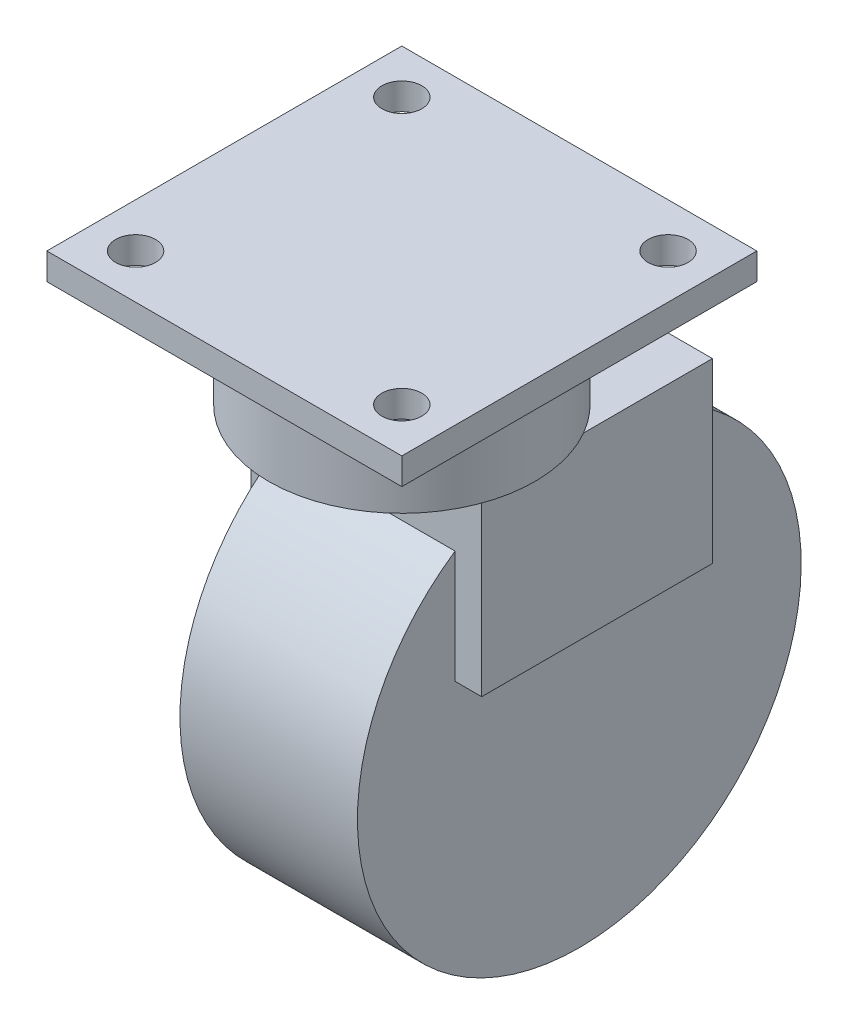
SolidWorks part; units mm, degrees
ref_plane "Front Plane" through (0, 0, 0) normal (0, 0, 1) x (1, 0, 0)
ref_plane "Top Plane" through (0, 0, 0) normal (0, 1, 0) x (1, 0, 0)
ref_plane "Right Plane" through (0, 0, 0) normal (1, 0, 0) x (0, 0, -1)
sketch "SK_Plate" plane through (0, 0, 0) normal (0, 1, 0) x (1, 0, 0)
  line L1 (-20, 20) -> (20, 20)
  line L2 (-20, 20) -> (-20, -20)
  line L3 (-20, -20) -> (20, -20)
  line L4 (20, 20) -> (20, -20)
  dimension "D1" = 40
  dimension "D2" = 40
  dimension "D3" = 20
  dimension "D4" = 20
extrude "EX_Plate" add sketch "SK_Plate" against normal blind 3
sketch "SK_PlateHoles_4x" plane through (0, 0, 0) normal (0, 1, 0) x (1, 0, 0)
  circle A0 centre (15, -15) radius 2.25
  circle A1 centre (-15, -15) radius 2.25
  circle A2 centre (15, 15) radius 2.25
  circle A3 centre (-15, 15) radius 2.25
  dimension "D3" = 4.5
  dimension "D6" = 4.5
  dimension "D9" = 4.5
  dimension "D12" = 4.5
  dimension "D1" = 15
  dimension "D2" = 15
  dimension "D4" = 15
  dimension "D5" = 15
  dimension "D7" = 15
  dimension "D8" = 15
  dimension "D10" = 15
  dimension "D11" = 15
extrude "CUT_PlateHoles_4x" cut sketch "SK_PlateHoles_4x" against normal blind 3
ref_plane "PL_Zm3" through (0, -3, 0) normal (0, 1, 0) x (1, 0, 0)
sketch "SK_Swivel" plane through (0, -3, 0) normal (0, 1, 0) x (1, 0, 0)
  circle A0 centre (0, 0) radius 15
  dimension "D1" = 30
extrude "EX_Swivel" add sketch "SK_Swivel" against normal blind 12
ref_plane "PL_Zm15" through (0, -15, 0) normal (0, 1, 0) x (1, 0, 0)
sketch "SK_Fork" plane through (0, -15, 0) normal (0, 1, 0) x (1, 0, 0)
  line L1 (-13, 22) -> (13, 22)
  line L2 (-13, 22) -> (-13, -4)
  line L3 (-13, -4) -> (13, -4)
  line L4 (13, 22) -> (13, -4)
  dimension "D1" = 26
  dimension "D2" = 26
  dimension "D3" = 22
  dimension "D4" = 13
extrude "EX_Fork" add sketch "SK_Fork" against normal blind 20
ref_plane "PL_Ym10" through (-10, 0, 0) normal (1, 0, 0) x (0, 0, -1)
sketch "SK_Wheel" plane through (-10, 0, 0) normal (1, 0, 0) x (0, 0, -1)
  circle A0 centre (10, -43) radius 25
  dimension "D3" = 50
  dimension "D1" = 10
  dimension "D2" = 43
extrude "EX_Wheel" add sketch "SK_Wheel" along normal blind 20
ref_axis "AX_X" through (0, 0, -37.75) along (0, 0, 1)
ref_axis "AX_Y" through (22, 0, 0) along (-1, 0, 0)
ref_axis "AX_Z" through (0, 3.4, 0) along (0, -1, 0)
ref_plane "PL_Zm43" through (0, -43, 0) normal (0, 1, 0) x (1, 0, 0)
sketch "SK_F_IF_Axle" plane through (0, -43, 0) normal (0, 1, 0) x (1, 0, 0)
  point P0 (0, 10)
  dimension "D1" = 10
